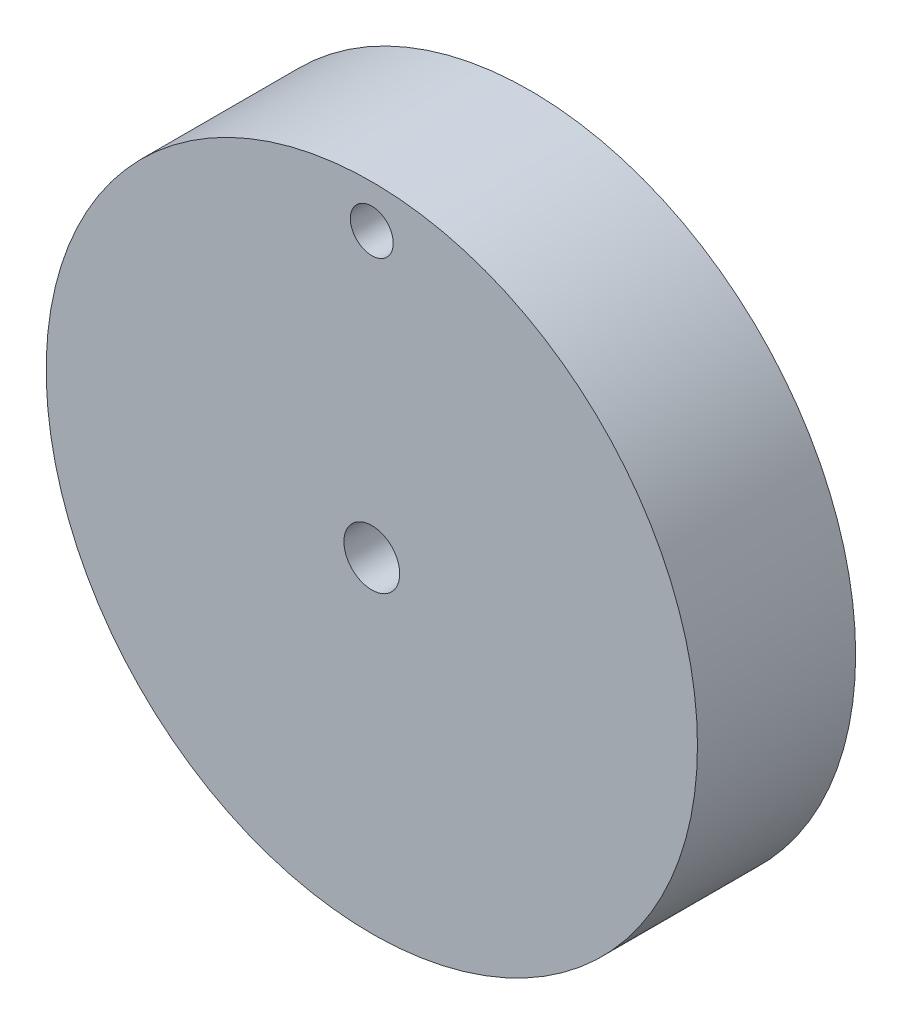
SolidWorks part; units mm, degrees
ref_plane "Front Plane" through (0, 0, 0) normal (0, 0, 1) x (1, 0, 0)
ref_plane "Top Plane" through (0, 0, 0) normal (0, 1, 0) x (1, 0, 0)
ref_plane "Right Plane" through (0, 0, 0) normal (1, 0, 0) x (0, 0, -1)
sketch "Sketch1" plane through (0, 0, 0) normal (0, 0, 1) x (1, 0, 0)
  circle A0 centre (0, 0) radius 18
extrude "Boss-Extrude1" add sketch "Sketch1" along normal blind 20
sketch "Sketch2" plane through (0, 0, 20) normal (0, 0, 1) x (1, 0, 0)
  circle A0 centre (0, 0) radius 3
extrude "Cut-Extrude1" cut sketch "Sketch2" against normal blind 60
sketch "Sketch4" plane through (0, 0, 20) normal (0, 0, 1) x (1, 0, 0)
  circle A0 centre (0, 0) radius 14.576
  circle A1 centre (0, 0) radius 35
extrude "Boss-Extrude2" add sketch "Sketch4" against normal blind 17
sketch "Sketch5" plane through (0, 0, 20) normal (0, 0, 1) x (1, 0, 0)
  circle A0 centre (0, 30.4201) radius 2.3042
extrude "Cut-Extrude2" cut sketch "Sketch5" against normal blind 4
